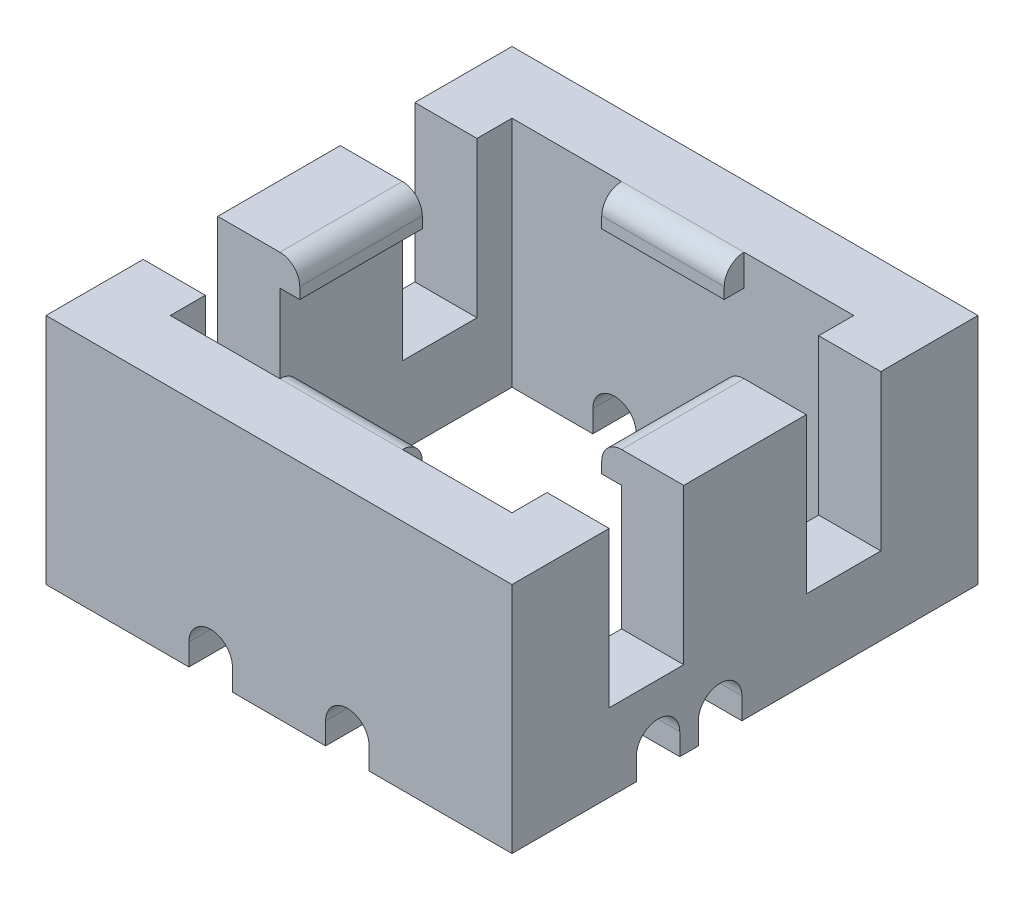
SolidWorks part; units mm, degrees
ref_plane "Front Plane" through (0, 0, 0) normal (0, 0, 1) x (1, 0, 0)
ref_plane "Top Plane" through (0, 0, 0) normal (0, 1, 0) x (1, 0, 0)
ref_plane "Right Plane" through (0, 0, 0) normal (1, 0, 0) x (0, 0, -1)
sketch "Sketch1" plane through (0, 0, 0) normal (0, 1, 0) x (1, 0, 0)
  line L0 (0.8128, 1.0616) -> (0.8128, -0.3709)
  line L1 (0.8128, -0.3709) -> (5.2934, -0.3709)
  line L26 (-1.7272, 1.0616) -> (0.8128, 1.0616)
  line L30 (7.7978, 0.4419) -> (5.2934, 0.4419)
  line L35 (5.2934, -0.3709) -> (5.2934, 0.4419)
  line L37 (-1.7272, 6.6141) -> (1.6256, 6.6141)
  line L38 (7.7978, 0.4419) -> (7.7978, -2.9109)
  line L39 (7.7978, 0.4419) -> (7.7978, 7.4269) construction
  line L42 (1.6256, 6.6141) -> (1.6256, 4.1096)
  line L45 (-1.7272, -2.9109) -> (7.7978, -2.9109)
  line L47 (-1.7272, 6.6141) -> (-1.7272, 4.1096)
  line L48 (-1.7272, 4.1096) -> (1.6256, 4.1096)
  line L49 (-1.7272, 1.0616) -> (-1.7272, -2.9109)
  dimension "D2" = 0.8128
  dimension "D3" = 3.3528
  dimension "D4" = 2.5044
  dimension "D5" = 6.985
  dimension "D6" = 2.54
  dimension "D7" = 2.54
  dimension "D8" = 2.5044
  dimension "D10" = 6.985
  dimension "D16" = 3.048
extrude "Boss-Extrude1" add sketch "Sketch1" along normal blind 1.27
fillet "Fillet3" radius 0.8128 1 edges at (6.5456, 1.27, -0.4419)
fillet "Fillet4" radius 0.8128 1 edges at (1.6256, 1.27, -5.3619)
mirror "Mirror6" about plane through (7.7978, 1.27, -0.4419) normal (-1, 0, 0) of bodies 103 102
mirror "Mirror7" about plane through (17.3228, 1.27, -6.6141) normal (0, 0, 1) of bodies 112 113
mirror "Mirror8" about plane through (7.7978, 1.27, -12.7863) normal (1, 0, 0) of bodies 114 115
sketch "Sketch5" plane through (0, 0, 0) normal (0, -1, 0) x (1, 0, 0)
  line L0 (17.3228, -1.0616) -> (14.7828, -1.0616)
  line L1 (17.3228, 2.9109) -> (-1.7272, 2.9109)
  line L2 (17.3228, 2.9109) -> (17.3228, -1.0616)
  line L3 (17.3228, -16.1391) -> (-1.7272, -16.1391)
  line L4 (-1.7272, 2.9109) -> (-1.7272, -1.0616)
  line L5 (14.7828, 0.3709) -> (0.8128, 0.3709)
  line L6 (14.7828, 0.3709) -> (14.7828, -1.0616)
  line L7 (14.7828, -13.5991) -> (0.8128, -13.5991)
  line L8 (0.8128, 0.3709) -> (0.8128, -1.0616)
  line L9 (17.3228, -4.1096) -> (14.7828, -4.1096)
  line L10 (17.3228, -4.1096) -> (13.97, -4.1096) construction
  line L11 (17.3228, -9.1185) -> (14.7828, -9.1185)
  line L12 (17.3228, -9.1185) -> (13.97, -9.1185) construction
  line L13 (17.3228, -12.1665) -> (14.7828, -12.1665)
  line L14 (0.8128, -12.1665) -> (-1.7272, -12.1665)
  line L15 (-1.7272, -9.1185) -> (0.8128, -9.1185)
  line L16 (-1.7272, -9.1185) -> (1.6256, -9.1185) construction
  line L17 (-1.7272, -4.1096) -> (0.8128, -4.1096)
  line L18 (-1.7272, -4.1096) -> (1.6256, -4.1096) construction
  line L19 (-1.7272, -1.0616) -> (0.8128, -1.0616)
  line L20 (17.3228, -4.1096) -> (17.3228, -9.1185)
  line L21 (14.7828, -4.1096) -> (14.7828, -9.1185)
  line L22 (17.3228, -12.1665) -> (17.3228, -16.1391)
  line L23 (14.7828, -12.1665) -> (14.7828, -13.5991)
  line L24 (0.8128, -12.1665) -> (0.8128, -13.5991)
  line L25 (-1.7272, -12.1665) -> (-1.7272, -16.1391)
  line L26 (0.8128, -4.1096) -> (0.8128, -9.1185)
  line L27 (-1.7272, -4.1096) -> (-1.7272, -9.1185)
extrude "Boss-Extrude3" add sketch "Sketch5" along normal blind 5.08
sketch "Sketch6" plane through (0, -5.08, 0) normal (0, -1, 0) x (1, 0, 0)
  line L1 (17.3228, 2.9109) -> (-1.7272, 2.9109)
  line L2 (17.3228, 2.9109) -> (17.3228, -16.1391)
  line L3 (17.3228, -16.1391) -> (-1.7272, -16.1391)
  line L4 (-1.7272, 2.9109) -> (-1.7272, -16.1391)
  line L5 (14.7828, 0.3709) -> (0.8128, 0.3709)
  line L6 (14.7828, 0.3709) -> (14.7828, -13.5991)
  line L7 (14.7828, -13.5991) -> (0.8128, -13.5991)
  line L8 (0.8128, 0.3709) -> (0.8128, -13.5991)
extrude "Boss-Extrude4" add sketch "Sketch6" along normal blind 3.175
sketch "Sketch7" plane through (0, -8.255, 0) normal (0, -1, 0) x (1, 0, 0)
  line L0 (-1.7272, 2.9109) -> (-1.7272, -16.1391) construction
  line L1 (-1.7272, -6.4871) -> (0.8128, -6.4871)
  line L2 (-1.7272, -6.4871) -> (-1.7272, -4.7091)
  line L3 (-1.7272, -4.7091) -> (0.8128, -4.7091)
  line L4 (0.8128, -6.4871) -> (0.8128, -4.7091)
  line L5 (0.8128, 0.3709) -> (0.8128, -13.5991) construction
  line L6 (17.3228, 2.9109) -> (-1.7272, 2.9109) construction
  line L7 (-1.7272, -3.9471) -> (0.8128, -3.9471)
  line L8 (-1.7272, -3.9471) -> (-1.7272, -2.1691)
  line L9 (-1.7272, -2.1691) -> (0.8128, -2.1691)
  line L10 (0.8128, -3.9471) -> (0.8128, -2.1691)
  line L11 (9.7028, 2.9109) -> (11.4808, 2.9109)
  line L12 (9.7028, 2.9109) -> (9.7028, 0.3709)
  line L13 (9.7028, 0.3709) -> (11.4808, 0.3709)
  line L14 (11.4808, 2.9109) -> (11.4808, 0.3709)
  line L15 (14.7828, 0.3709) -> (0.8128, 0.3709) construction
  line L16 (0.8128, -13.5991) -> (14.7828, -13.5991) construction
  line L18 (4.1148, 2.9109) -> (5.8928, 2.9109)
  line L19 (4.1148, 2.9109) -> (4.1148, 0.3709)
  line L20 (4.1148, 0.3709) -> (5.8928, 0.3709)
  line L21 (5.8928, 2.9109) -> (5.8928, 0.3709)
  line L22 (9.7028, -13.5991) -> (11.4808, -13.5991)
  line L23 (9.7028, -13.5991) -> (9.7028, -16.1391)
  line L24 (9.7028, -16.1391) -> (11.4808, -16.1391)
  line L25 (-1.7272, -16.1391) -> (17.3228, -16.1391) construction
  line L26 (14.7828, -13.5991) -> (14.7828, 0.3709) construction
  line L27 (5.8928, -13.5991) -> (4.1148, -13.5991)
  line L28 (5.8928, -13.5991) -> (5.8928, -16.1391)
  line L29 (5.8928, -16.1391) -> (4.1148, -16.1391)
  line L30 (4.1148, -13.5991) -> (4.1148, -16.1391)
  line L31 (14.7828, -6.4871) -> (17.3228, -6.4871)
  line L32 (14.7828, -6.4871) -> (14.7828, -4.7091)
  line L33 (14.7828, -4.7091) -> (17.3228, -4.7091)
  line L34 (17.3228, -6.4871) -> (17.3228, -4.7091)
  line L35 (17.3228, -16.1391) -> (17.3228, 2.9109) construction
  line L36 (11.4808, -13.5991) -> (11.4808, -16.1391)
  line L37 (14.7828, -3.9471) -> (17.3228, -3.9471)
  line L38 (14.7828, -3.9471) -> (14.7828, -2.1691)
  line L39 (14.7828, -2.1691) -> (17.3228, -2.1691)
  line L40 (17.3228, -3.9471) -> (17.3228, -2.1691)
  dimension "D2" = 1.778
  dimension "D3" = 2.54
  dimension "D4" = 1.778
  dimension "D5" = 1.778
  dimension "D6" = 1.778
  dimension "D7" = 2.54
  dimension "D8" = 1.778
  dimension "D9" = 3.302
  dimension "D10" = 3.302
  dimension "D11" = 1.778
  dimension "D12" = 1.778
  dimension "D13" = 1.778
  dimension "D14" = 3.302
  dimension "D15" = 3.302
  dimension "D16" = 0.762
  dimension "D17" = 0.762
extrude "Cut-Extrude2" cut sketch "Sketch7" against normal blind 1.778
fillet "Fillet6" radius 0.889 16 edges at (-0.4572, -6.477, -4.7091) (16.0528, -6.477, -4.7091) (11.4808, -6.477, 1.6409) (5.8928, -6.477, 1.6409) (9.7028, -6.477, 1.6409) (4.1148, -6.477, 1.6409) (-0.4572, -6.477, -2.1691) (16.0528, -6.477, -2.1691) (-0.4572, -6.477, -6.4871) (-0.4572, -6.477, -3.9471) (16.0528, -6.477, -3.9471) (16.0528, -6.477, -6.4871) (4.1148, -6.477, -14.8691) (9.7028, -6.477, -14.8691) (5.8928, -6.477, -14.8691) (11.4808, -6.477, -14.8691)
